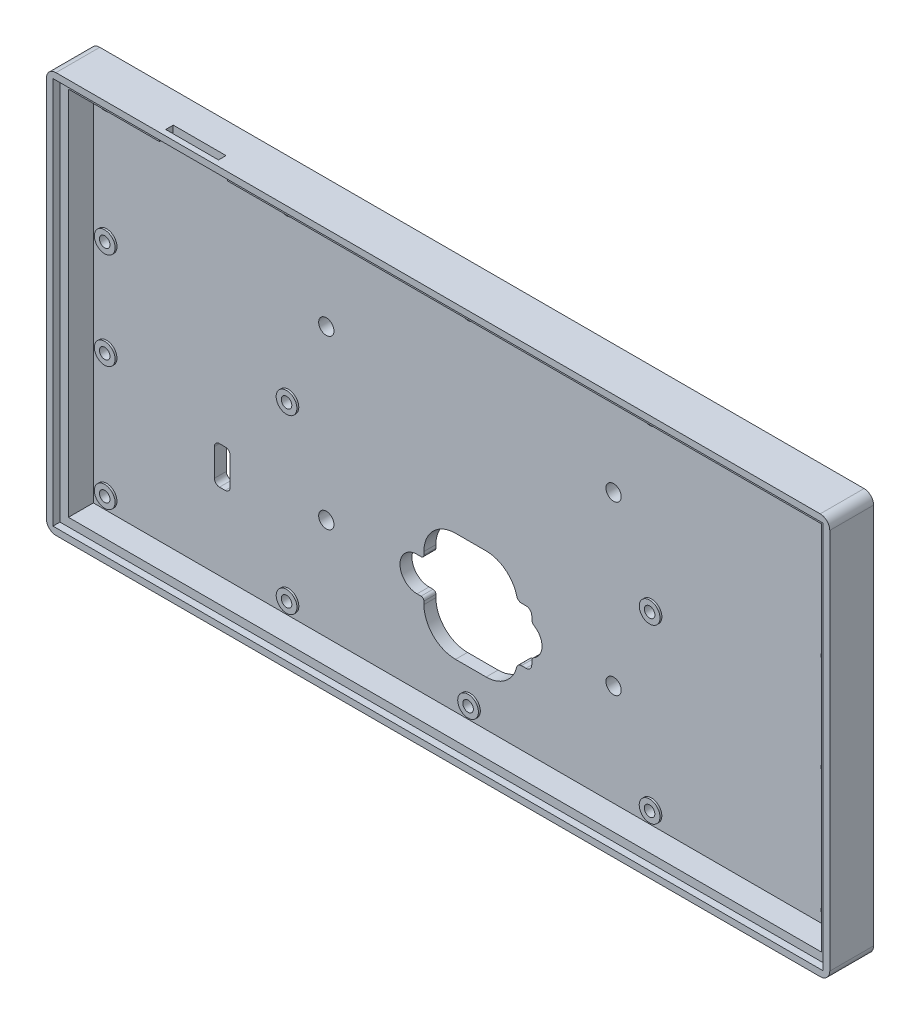
SolidWorks part; units mm, degrees
ref_plane "Front Plane" through (0, 0, 0) normal (0, 0, 1) x (1, 0, 0)
ref_plane "Top Plane" through (0, 0, 0) normal (0, 1, 0) x (1, 0, 0)
ref_plane "Right Plane" through (0, 0, 0) normal (1, 0, 0) x (0, 0, -1)
sketch "PCB" plane through (0, 0, 0) normal (0, 0, 1) x (1, 0, 0)
  line L0 (96.2635, 45.5524) -> (101.8921, 45.5524) construction
  line L1 (-101.8921, 51.181) -> (101.8921, 51.181) construction
  line L2 (-101.8921, 51.181) -> (-101.8921, -51.181) construction
  line L3 (-101.8921, -51.181) -> (101.8921, -51.181) construction
  line L4 (101.8921, 51.181) -> (101.8921, -51.181) construction
  line L5 (-101.8921, 51.181) -> (101.8921, -51.181) construction
  line L6 (-101.8921, -51.181) -> (101.8921, 51.181) construction
  line L7 (96.2635, 45.5524) -> (96.2635, 51.181) construction
  line L8 (-96.2635, 45.5524) -> (-101.8921, 45.5524) construction
  line L9 (-96.2635, -45.5524) -> (-96.2635, -51.181) construction
  line L10 (-92.8243, 0) -> (-92.8243, 25.6794) construction
  line L11 (-98.8568, 31.7119) -> (-86.7918, 31.7119)
  line L12 (-98.8568, 31.7119) -> (-98.8568, 19.6469)
  line L13 (-98.8568, 19.6469) -> (-86.7918, 19.6469)
  line L14 (-86.7918, 31.7119) -> (-86.7918, 19.6469)
  line L15 (-98.8568, 31.7119) -> (-86.7918, 19.6469) construction
  line L16 (-98.8568, 19.6469) -> (-86.7918, 31.7119) construction
  line L17 (-98.8568, 6.0325) -> (-86.7918, 6.0325)
  line L18 (-98.8568, 6.0325) -> (-98.8568, -6.0325)
  line L19 (-98.8568, -6.0325) -> (-86.7918, -6.0325)
  line L20 (-86.7918, 6.0325) -> (-86.7918, -6.0325)
  line L21 (-98.8568, 6.0325) -> (-86.7918, -6.0325) construction
  line L22 (-98.8568, -6.0325) -> (-86.7918, 6.0325) construction
  line L23 (-98.8568, -19.6469) -> (-86.7918, -19.6469)
  line L24 (-98.8568, -19.6469) -> (-98.8568, -31.7119)
  line L25 (-98.8568, -31.7119) -> (-86.7918, -31.7119)
  line L26 (-86.7918, -19.6469) -> (-86.7918, -31.7119)
  line L27 (-98.8568, -19.6469) -> (-86.7918, -31.7119) construction
  line L28 (-98.8568, -31.7119) -> (-86.7918, -19.6469) construction
  line L29 (86.7918, 31.7119) -> (98.8568, 31.7119)
  line L30 (86.7918, 31.7119) -> (86.7918, 19.6469)
  line L31 (86.7918, 19.6469) -> (98.8568, 19.6469)
  line L32 (98.8568, 31.7119) -> (98.8568, 19.6469)
  line L33 (86.7918, 31.7119) -> (98.8568, 19.6469) construction
  line L34 (86.7918, 19.6469) -> (98.8568, 31.7119) construction
  line L35 (86.7918, 6.0325) -> (98.8568, 6.0325)
  line L36 (86.7918, 6.0325) -> (86.7918, -6.0325)
  line L37 (86.7918, -6.0325) -> (98.8568, -6.0325)
  line L38 (98.8568, 6.0325) -> (98.8568, -6.0325)
  line L39 (86.7918, 6.0325) -> (98.8568, -6.0325) construction
  line L40 (86.7918, -6.0325) -> (98.8568, 6.0325) construction
  line L41 (86.7918, -19.6469) -> (98.8568, -19.6469)
  line L42 (86.7918, -19.6469) -> (86.7918, -31.7119)
  line L43 (86.7918, -31.7119) -> (98.8568, -31.7119)
  line L44 (98.8568, -19.6469) -> (98.8568, -31.7119)
  line L45 (86.7918, -19.6469) -> (98.8568, -31.7119) construction
  line L46 (86.7918, -31.7119) -> (98.8568, -19.6469) construction
  line L47 (-92.8243, 0) -> (-92.8243, -25.6794) construction
  line L48 (-92.8243, 25.6794) -> (-101.8921, 25.6794) construction
  line L49 (92.8243, 25.6794) -> (101.8921, 25.6794) construction
  line L50 (-3.114, -17.4711) -> (-3.114, -27.7327) construction
  circle A0 centre (-96.2635, 45.5524) radius 0.9995
  circle A1 centre (-96.2635, -45.5524) radius 0.9995
  circle A2 centre (96.2635, -45.5524) radius 0.9995
  circle A3 centre (96.2635, 45.5524) radius 0.9995
  circle A4 centre (-3.114, -17.4711) radius 1.9939
  circle A5 centre (-3.114, -27.7327) radius 1.9939
  point P0 (0, 0)
  point P14 (-92.8243, 25.6794)
  point P23 (-92.8243, 0)
  point P28 (-92.8243, -25.6794)
  point P33 (92.8243, 25.6794)
  point P38 (92.8243, 0)
  point P43 (92.8243, -25.6794)
  point P54 (0.1092, -22.6019)
  point P55 (-7.5006, -22.6019)
  point P60 (-3.114, -22.6019)
  dimension "D4" = 1.999
  dimension "D14" = 3.9878
  dimension "D1" = 203.7842
  dimension "D2" = 102.362
  dimension "D3" = 5.6286
  dimension "D5" = 25.5016
  dimension "D6" = 25.5016
  dimension "D7" = 9.0678
  dimension "D8" = 12.065
  dimension "D9" = 102.0013
  dimension "D10" = 28.5791
  dimension "D11" = 7.6098
  dimension "D12" = 5.1308
  dimension "D13" = 3.2233
sketch "DT_plug" plane through (0, 0, 0) normal (0, 0, 1) x (1, 0, 0)
  line L0 (29.2774, -40.0231) -> (29.2774, -5.0981) construction
  dimension "D1" = 34.925
sketch "display_screen" plane through (0, 0, 0) normal (0, 0, 1) x (1, 0, 0)
  line L1 (-80.3275, 46.3296) -> (83.7565, 46.3296) construction
  line L2 (-80.3275, 46.3296) -> (-80.3275, -50.9016) construction
  line L3 (-80.3275, -50.9016) -> (83.7565, -50.9016) construction
  line L4 (83.7565, 46.3296) -> (83.7565, -50.9016) construction
  line L5 (-78.2955, 44.2976) -> (78.2955, 44.2976) construction
  line L6 (-78.2955, 44.2976) -> (-78.2955, -44.2976) construction
  line L7 (-78.2955, -44.2976) -> (78.2955, -44.2976) construction
  line L8 (78.2955, 44.2976) -> (78.2955, -44.2976) construction
  point P8 (0, 44.2976)
  point P10 (-78.2955, 0)
  dimension "D1" = 164.084
  dimension "D2" = 97.2312
  dimension "D3" = 6.604
  dimension "D4" = 2.032
  dimension "D5" = 2.032
  dimension "D6" = 5.461
ref_plane "back_of_PCB" through (0, 0, -1.8542) normal (0, 0, 1) x (1, 0, 0)
ref_plane "back_PCB_clearance" through (0, 0, -8.4582) normal (0, 0, 1) x (1, 0, 0)
sketch "Sketch4" plane through (0, 0, 0) normal (0, 0, 1) x (1, 0, 0)
  line L0 (-102.1461, 51.4096) -> (-102.1461, 53.1596) construction
  line L1 (-102.1461, 51.4096) -> (102.1461, 51.4096)
  line L2 (-102.1461, 51.4096) -> (-102.1461, -51.4096)
  line L3 (-102.1461, -51.4096) -> (102.1461, -51.4096)
  line L4 (102.1461, 51.4096) -> (102.1461, -51.4096)
  line L5 (-103.8961, 53.1596) -> (103.8961, 53.1596)
  line L6 (-103.8961, 53.1596) -> (-103.8961, -53.1596)
  line L7 (-103.8961, -53.1596) -> (103.8961, -53.1596)
  line L8 (103.8961, 53.1596) -> (103.8961, -53.1596)
  line L9 (-102.1461, 51.4096) -> (-103.8961, 51.4096) construction
  line L10 (102.1461, -51.4096) -> (102.1461, -53.1596) construction
  line L11 (102.1461, -51.4096) -> (103.8961, -51.4096) construction
  line L12 (-101.8921, 51.181) -> (101.8921, 51.181) construction
  line L13 (-101.8921, 51.181) -> (-101.8921, -51.181) construction
  line L14 (101.8921, 51.181) -> (101.8921, -51.181) construction
  line L15 (-101.8921, -51.181) -> (101.8921, -51.181) construction
  dimension "D1" = 1.75
  dimension "D2" = 0.2286
  dimension "D3" = 0.254
  dimension "D4" = 0.254
  dimension "D5" = 0.2286
extrude "Boss-Extrude1" add sketch "Sketch4" against normal up to surface (1.8542 mm away) up to plane "back_of_PCB"
sketch "Sketch5" plane through (0, 0, -1.8542) normal (0, 0, -1) x (-1, 0, 0)
  line L1 (-103.8961, 53.1596) -> (103.8961, 53.1596)
  line L2 (-103.8961, 53.1596) -> (-103.8961, -53.1596)
  line L3 (-103.8961, -53.1596) -> (103.8961, -53.1596)
  line L4 (103.8961, 53.1596) -> (103.8961, -53.1596)
  line L6 (101.8921, 51.181) -> (-101.8921, 51.181) construction
  line L7 (-99.8931, 49.182) -> (99.8931, 49.182)
  line L8 (-99.8931, 49.182) -> (-99.8931, -49.182)
  line L9 (-99.8931, -49.182) -> (99.8931, -49.182)
  line L10 (99.8931, 49.182) -> (99.8931, -49.182)
  line L11 (-99.8931, 49.182) -> (-99.8931, 51.181) construction
  line L12 (-99.8931, 49.182) -> (-101.8921, 49.182) construction
  line L13 (-101.8921, 51.181) -> (-101.8921, -51.181) construction
  line L14 (99.8931, -49.182) -> (101.8921, -49.182) construction
  line L15 (101.8921, 51.181) -> (101.8921, -51.181) construction
  line L16 (99.8931, -49.182) -> (99.8931, -51.181) construction
  line L17 (101.8921, -51.181) -> (-101.8921, -51.181) construction
  dimension "D1" = 1.999
extrude "Boss-Extrude2" add sketch "Sketch5" along normal up to surface (6.604 mm away) up to plane "back_PCB_clearance"
sketch "Sketch6" plane through (0, 0, -8.4582) normal (0, 0, -1) x (-1, 0, 0)
  line L0 (11.7018, -27.8978) -> (11.7018, -28.6979) construction
  line L1 (-103.8961, 53.1596) -> (103.8961, 53.1596)
  line L2 (-103.8961, 53.1596) -> (-103.8961, -53.1596)
  line L3 (-103.8961, -53.1596) -> (103.8961, -53.1596)
  line L4 (103.8961, 53.1596) -> (103.8961, -53.1596)
  line L5 (3.8278, -8.6319) -> (-4.2865, -8.6319) construction
  line L6 (11.7018, -16.5059) -> (11.7018, -17.306) construction
  line L7 (3.8278, -36.5719) -> (-4.2865, -36.5719) construction
  line L11 (12.9718, -18.576) -> (14.0259, -18.576) construction
  line L13 (12.9718, -26.6278) -> (14.0259, -26.6278) construction
  line L15 (-13.6655, -15.9344) -> (-14.8666, -15.9344) construction
  line L16 (-15.8826, -27.4219) -> (-15.8826, -28.2534) construction
  line L17 (-13.6655, -29.2694) -> (-14.8666, -29.2694) construction
  line L18 (-15.8826, -16.9504) -> (-15.8826, -17.782) construction
  line L20 (12.2098, -27.8978) -> (12.2098, -28.6979)
  line L21 (3.8278, -37.0799) -> (-4.2865, -37.0799)
  line L22 (-13.6655, -29.7774) -> (-14.8666, -29.7774)
  line L23 (-16.3906, -27.4219) -> (-16.3906, -28.2534)
  line L24 (-16.3906, -16.9504) -> (-16.3906, -17.782)
  line L25 (-13.6655, -15.4264) -> (-14.8666, -15.4264)
  line L26 (3.8278, -8.1239) -> (-4.2865, -8.1239)
  line L27 (12.2098, -16.5059) -> (12.2098, -17.306)
  line L28 (12.9718, -18.068) -> (14.0259, -18.068)
  line L29 (12.9718, -27.1358) -> (14.0259, -27.1358)
  arc A0 (-16.7989, -19.407) -> (-16.7989, -25.7969) centre (-14.8666, -22.6019) ccw construction
  arc A1 (12.9718, -18.576) -> (11.7018, -17.306) centre (12.9718, -17.306) cw construction
  arc A2 (12.9718, -26.6278) -> (11.7018, -27.8978) centre (12.9718, -27.8978) ccw construction
  arc A3 (14.0259, -26.6278) -> (14.0259, -18.576) centre (14.0259, -22.6019) ccw construction
  arc A4 (11.7018, -28.6979) -> (3.8278, -36.5719) centre (3.8278, -28.6979) cw construction
  arc A5 (11.7018, -16.5059) -> (3.8278, -8.6319) centre (3.8278, -16.5059) ccw construction
  arc A6 (-4.2865, -8.6319) -> (-11.9202, -14.5755) centre (-4.2865, -16.5059) ccw construction
  arc A7 (-11.9202, -14.5755) -> (-13.6655, -15.9344) centre (-13.6655, -14.1342) cw construction
  arc A8 (-4.2865, -36.5719) -> (-11.9202, -30.6283) centre (-4.2865, -28.6979) cw construction
  arc A9 (-11.9202, -30.6283) -> (-13.6655, -29.2694) centre (-13.6655, -31.0697) ccw construction
  arc A10 (-14.8666, -15.9344) -> (-15.8826, -16.9504) centre (-14.8666, -16.9504) ccw construction
  arc A11 (-15.8826, -17.782) -> (-16.7989, -19.407) centre (-17.7817, -17.782) cw construction
  arc A12 (-15.8826, -27.4219) -> (-16.7989, -25.7969) centre (-17.7817, -27.4219) ccw construction
  arc A13 (-15.8826, -28.2534) -> (-14.8666, -29.2694) centre (-14.8666, -28.2534) ccw construction
  arc A14 (12.2098, -28.6979) -> (3.8278, -37.0799) centre (3.8278, -28.6979) cw
  arc A15 (-4.2865, -37.0799) -> (-12.4127, -30.7529) centre (-4.2865, -28.6979) cw
  arc A16 (-12.4127, -30.7529) -> (-13.6655, -29.7774) centre (-13.6655, -31.0697) ccw
  arc A17 (-16.3906, -28.2534) -> (-14.8666, -29.7774) centre (-14.8666, -28.2534) ccw
  arc A18 (-16.3906, -27.4219) -> (-17.0618, -26.2315) centre (-17.7817, -27.4219) ccw
  arc A19 (-17.0618, -18.9723) -> (-17.0618, -26.2315) centre (-14.8666, -22.6019) ccw
  arc A20 (-16.3906, -17.782) -> (-17.0618, -18.9723) centre (-17.7817, -17.782) cw
  arc A21 (-14.8666, -15.4264) -> (-16.3906, -16.9504) centre (-14.8666, -16.9504) ccw
  arc A22 (-12.4127, -14.451) -> (-13.6655, -15.4264) centre (-13.6655, -14.1342) cw
  arc A23 (-4.2865, -8.1239) -> (-12.4127, -14.451) centre (-4.2865, -16.5059) ccw
  arc A24 (12.2098, -16.5059) -> (3.8278, -8.1239) centre (3.8278, -16.5059) ccw
  arc A25 (12.9718, -18.068) -> (12.2098, -17.306) centre (12.9718, -17.306) cw
  arc A26 (14.0259, -27.1358) -> (14.0259, -18.068) centre (14.0259, -22.6019) ccw
  arc A27 (12.9718, -27.1358) -> (12.2098, -27.8978) centre (12.9718, -27.8978) ccw
  point P6 (-0.1092, -22.6019)
  dimension "D7" = 3.7338
  dimension "D9" = 1.27
  dimension "D3" = 1.0541
  dimension "D10" = 7.874
  dimension "D13" = 1.8002
  dimension "D16" = 1.016
  dimension "D17" = 1.8991
  dimension "D2" = 11.811
  dimension "D4" = 13.97
  dimension "D5" = 15.7734
  dimension "D6" = 6.6675
  dimension "D8" = 1.016
  dimension "D11" = 0.8001
  dimension "D12" = 13.97
  dimension "D14" = 8.1143
  dimension "D15" = 6.6675
  dimension "D22" = 0.508
extrude "Boss-Extrude3" add sketch "Sketch6" along normal blind 3.175
sketch "Sketch10" plane through (0, 0, -11.6332) normal (0, 0, -1) x (-1, 0, 0)
  line L0 (-38.1, 22.225) -> (38.1, 22.225) construction
  line L1 (38.1, 22.225) -> (38.1, -22.225) construction
  line L3 (38.1, 22.225) -> (38.1, 53.1596) construction
  line L4 (-103.8961, 53.1596) -> (103.8961, 53.1596) construction
  line L5 (38.1, -22.225) -> (38.1, -53.1596) construction
  line L6 (103.8961, -53.1596) -> (-103.8961, -53.1596) construction
  circle A0 centre (-38.1, 22.225) radius 2.032
  circle A1 centre (-38.1, 22.225) radius 5.207 construction
  circle A2 centre (-38.1, -22.225) radius 5.207 construction
  circle A3 centre (-38.1, -22.225) radius 2.032
  circle A4 centre (38.1, -22.225) radius 2.032
  circle A5 centre (38.1, -22.225) radius 5.207 construction
  circle A6 centre (38.1, 22.225) radius 2.032
  circle A7 centre (38.1, 22.225) radius 5.207 construction
  point P12 (0, 22.225)
  dimension "D1" = 4.064
  dimension "D2" = 3.175
  dimension "D3" = 76.2
  dimension "D4" = 44.45
extrude "Cut-Extrude1" cut sketch "Sketch10" against normal up to next
fillet "Fillet1" radius 2.54 4 edges at (103.8961, 53.1596, -5.8166) (103.8961, -53.1596, -5.8166) (-103.8961, -53.1596, -5.8166) (-103.8961, 53.1596, -5.8166)
sketch "Sketch11" plane through (0, 0, -8.4582) normal (0, 0, 1) x (1, 0, 0)
  line L0 (-96.3835, 45.671) -> (-96.3835, 51.4096) construction
  line L1 (-96.3835, 45.671) -> (96.3835, 45.671) construction
  line L2 (-96.3835, 45.671) -> (-96.3835, -45.671) construction
  line L3 (-96.3835, -45.671) -> (96.3835, -45.671) construction
  line L4 (96.3835, 45.671) -> (96.3835, -45.671) construction
  line L5 (-102.1461, 51.4096) -> (102.1461, 51.4096) construction
  line L6 (-96.3835, 45.671) -> (-102.1461, 45.671) construction
  line L7 (-102.1461, 51.4096) -> (-102.1461, -51.4096) construction
  line L8 (96.3835, -45.671) -> (102.1461, -45.671) construction
  line L9 (102.1461, -51.4096) -> (102.1461, 51.4096) construction
  line L10 (96.3835, -45.671) -> (96.3835, -51.4096) construction
  line L11 (102.1461, -51.4096) -> (-102.1461, -51.4096) construction
  circle A0 centre (-96.3835, 45.671) radius 1.4
  circle A1 centre (0, 45.671) radius 1.4
  circle A2 centre (96.3835, 45.671) radius 1.4
  circle A3 centre (-96.3835, -45.671) radius 1.4
  circle A4 centre (96.3835, -45.671) radius 1.4
  circle A5 centre (96.3835, -12.808) radius 1.4
  circle A6 centre (96.3835, 12.808) radius 1.4
  circle A7 centre (0, -45.671) radius 1.4
  circle A8 centre (-96.3835, -12.808) radius 1.4
  circle A9 centre (-96.3835, 12.808) radius 1.4
  circle A10 centre (-48.1435, 45.671) radius 1.4
  circle A11 centre (48.1435, 45.671) radius 1.4
  circle A12 centre (48.1435, -45.671) radius 1.4
  circle A13 centre (-48.1435, -45.671) radius 1.4
  circle A14 centre (-48.1545, 0.033) radius 1.4
  circle A15 centre (48.1545, 0.033) radius 1.4
  dimension "D3" = 2.8
  dimension "D1" = 91.342
  dimension "D2" = 192.767
  dimension "D4" = 48.24
  dimension "D5" = 48.24
  dimension "D6" = 32.863
  dimension "D7" = 32.863
  dimension "D8" = 48.229
  dimension "D9" = 45.638
  dimension "D10" = 48.229
  dimension "D11" = 45.638
extrude "Cut-Extrude2" cut sketch "Sketch11" against normal up to next
sketch "Sketch12" plane through (0, 53.1596, 0) normal (0, 1, 0) x (1, 0, 0)
  line L0 (101.3561, 0) -> (-101.3561, 0) construction
  line L1 (-73.7461, 3.5) -> (-59.7461, 3.5)
  line L2 (-73.7461, 3.5) -> (-73.7461, 1.5)
  line L3 (-73.7461, 1.5) -> (-59.7461, 1.5)
  line L4 (-59.7461, 3.5) -> (-59.7461, 1.5)
  line L6 (-103.8961, 0) -> (-103.8961, 11.6332) construction
  dimension "D1" = 1.5
  dimension "D2" = 14
  dimension "D3" = 30.15
  dimension "D4" = 2
extrude "Cut-Extrude3" cut sketch "Sketch12" against normal up to next
sketch "Sketch13" plane through (0, 0, -1.8542) normal (0, 0, 1) x (1, 0, 0)
  line L0 (-59.7461, 51.4096) -> (102.1461, 51.4096) construction
  line L1 (-75.7461, 49.182) -> (-57.7461, 49.182)
  line L2 (-75.7461, 49.182) -> (-75.7461, 51.4096)
  line L3 (-75.7461, 51.4096) -> (-57.7461, 51.4096)
  line L4 (-57.7461, 49.182) -> (-57.7461, 51.4096)
  line L5 (99.8931, 49.182) -> (-99.8931, 49.182) construction
  line L6 (-73.7461, 51.4096) -> (-73.7461, 49.182) construction
  line L7 (-59.7461, 49.182) -> (-59.7461, 53.1596) construction
  dimension "D1" = 2
  dimension "D2" = 2
extrude "Cut-Extrude4" cut sketch "Sketch13" against normal up to surface (1.6458 mm away) up to face at (-66.7461, 51.1708, -3.5)
sketch "Sketch14" plane through (0, 0, -8.4582) normal (0, 0, 1) x (1, 0, 0)
  circle A0 centre (-96.3835, 45.671) radius 1.4
  circle A1 centre (-96.3835, 45.671) radius 2.75
  circle A3 centre (-96.3835, 45.671) radius 1.4 construction
  circle A4 centre (-48.1435, 45.671) radius 2.75
  circle A5 centre (-48.1435, 45.671) radius 1.4
  circle A6 centre (0, 45.671) radius 1.4
  circle A7 centre (0, 45.671) radius 2.75
  circle A8 centre (48.1435, 45.671) radius 1.4
  circle A9 centre (48.1435, 45.671) radius 2.75
  circle A10 centre (96.3835, 45.671) radius 1.4
  circle A11 centre (96.3835, 45.671) radius 2.75
  circle A12 centre (-96.3835, 12.808) radius 1.4
  circle A13 centre (-96.3835, 12.808) radius 2.75
  circle A14 centre (-48.1545, 0.033) radius 1.4
  circle A15 centre (-48.1545, 0.033) radius 2.75
  circle A16 centre (-96.3835, -12.808) radius 1.4
  circle A17 centre (-96.3835, -12.808) radius 2.75
  circle A18 centre (-96.3835, -45.671) radius 1.4
  circle A19 centre (-96.3835, -45.671) radius 2.75
  circle A20 centre (-48.1435, -45.671) radius 1.4
  circle A21 centre (-48.1435, -45.671) radius 2.75
  circle A22 centre (0, -45.671) radius 1.4
  circle A23 centre (0, -45.671) radius 2.75
  circle A24 centre (48.1545, 0.033) radius 1.4
  circle A25 centre (48.1545, 0.033) radius 2.75
  circle A26 centre (48.1435, -45.671) radius 1.4
  circle A27 centre (48.1435, -45.671) radius 2.75
  circle A28 centre (96.3835, -45.671) radius 1.4
  circle A29 centre (96.3835, -45.671) radius 2.75
  circle A30 centre (96.3835, -12.808) radius 1.4
  circle A31 centre (96.3835, -12.808) radius 2.75
  circle A32 centre (96.3835, 12.808) radius 1.4
  circle A33 centre (96.3835, 12.808) radius 2.75
  circle A34 centre (-48.1435, 45.671) radius 1.4 construction
  circle A35 centre (0, 45.671) radius 1.4 construction
  circle A36 centre (48.1435, 45.671) radius 1.4 construction
  circle A37 centre (96.3835, 45.671) radius 1.4 construction
  circle A38 centre (96.3835, 12.808) radius 1.4 construction
  circle A39 centre (48.1545, 0.033) radius 1.4 construction
  circle A40 centre (-48.1545, 0.033) radius 1.4 construction
  circle A41 centre (-96.3835, 12.808) radius 1.4 construction
  circle A42 centre (-96.3835, -12.808) radius 1.4 construction
  circle A43 centre (-96.3835, -45.671) radius 1.4 construction
  circle A44 centre (-48.1435, -45.671) radius 1.4 construction
  circle A45 centre (0, -45.671) radius 1.4 construction
  circle A46 centre (48.1435, -45.671) radius 1.4 construction
  circle A47 centre (96.3835, -45.671) radius 1.4 construction
  circle A48 centre (96.3835, -12.808) radius 1.4 construction
  dimension "D1" = 5.5
extrude "Boss-Extrude4" add sketch "Sketch14" along normal blind 0.5
sketch "Sketch15" plane through (0, 0, -8.4582) normal (0, 0, 1) x (1, 0, 0)
  line L0 (-99.8931, 49.182) -> (-99.8931, -49.182) construction
  line L1 (-66.4371, -18.827) -> (-64.9371, -18.827)
  line L2 (-67.7871, -20.177) -> (-67.7871, -27.477)
  line L3 (-66.4371, -28.827) -> (-64.9371, -28.827)
  line L4 (-63.5871, -20.177) -> (-63.5871, -27.477)
  line L5 (-99.8931, -49.182) -> (99.8931, -49.182) construction
  arc A0 (-64.9371, -28.827) -> (-63.5871, -27.477) centre (-64.9371, -27.477) ccw
  arc A1 (-67.7871, -27.477) -> (-66.4371, -28.827) centre (-66.4371, -27.477) ccw
  arc A2 (-66.4371, -18.827) -> (-67.7871, -20.177) centre (-66.4371, -20.177) ccw
  arc A3 (-64.9371, -18.827) -> (-63.5871, -20.177) centre (-64.9371, -20.177) cw
  point P10 (-63.5871, -28.827)
  point P13 (-67.7871, -28.827)
  point P16 (-67.7871, -18.827)
  dimension "D5" = 1.35
  dimension "D1" = 32.106
  dimension "D2" = 4.2
  dimension "D3" = 10
  dimension "D4" = 20.355
extrude "Cut-Extrude5" cut sketch "Sketch15" against normal up to next
